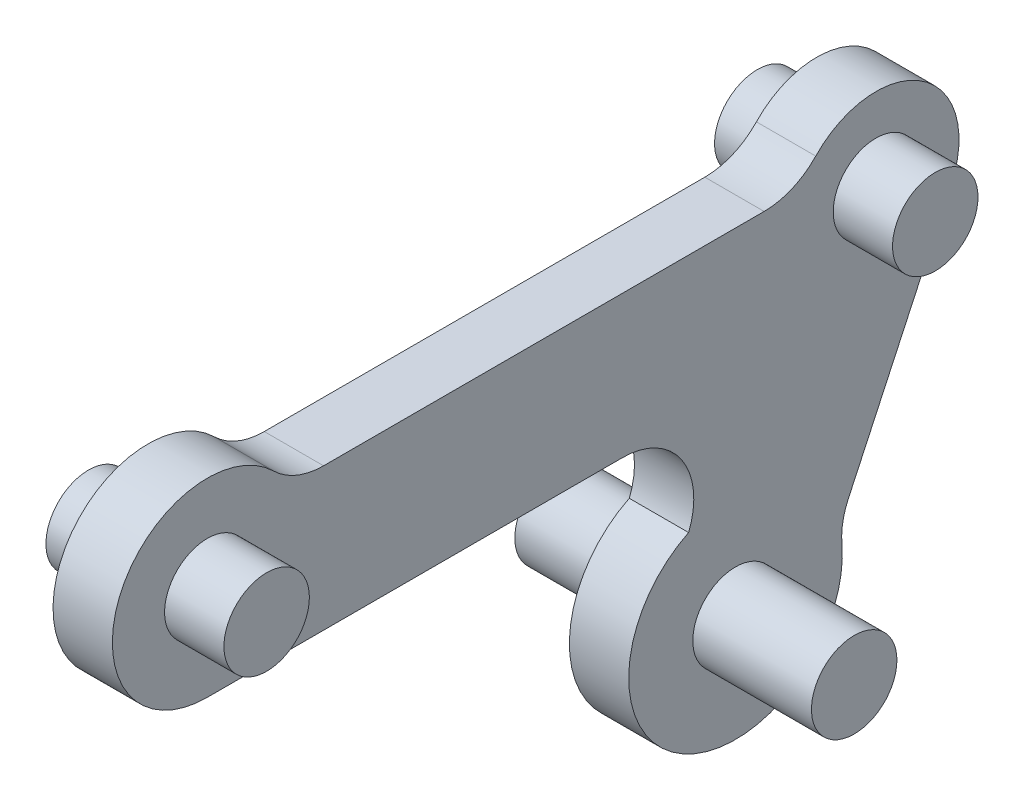
SolidWorks part; units mm, degrees
ref_plane "前视基准面" through (0, 0, 0) normal (0, 0, 1) x (1, 0, 0)
ref_plane "上视基准面" through (0, 0, 0) normal (0, 1, 0) x (1, 0, 0)
ref_plane "右视基准面" through (0, 0, 0) normal (1, 0, 0) x (0, 0, -1)
other "Configuration Table"
sketch "草图1" plane through (0, 0, 0) normal (1, 0, 0) x (0, 0, -1)
  line L1 (-28.1721, 1.4792) -> (-3.1721, 1.4792)
  line L2 (-28.1721, 1.4792) -> (-28.1721, -4.5208)
  line L3 (-28.1721, -4.5208) -> (-3.1721, -4.5208)
  line L4 (-3.1721, 1.4792) -> (-3.1721, -4.5208)
  line L5 (-3.1721, 1.4792) -> (3.1721, -1.4792)
  line L6 (-3.1721, 1.4792) -> (-9.0887, -11.2091)
  line L7 (-9.0887, -11.2091) -> (-2.7446, -14.1675)
  line L8 (3.1721, -1.4792) -> (-2.7446, -14.1675)
  circle A0 centre (-28.1721, -0.5208) radius 4
  circle A1 centre (0, 0) radius 3.5
  circle A2 centre (-5.9167, -12.6883) radius 4.5
  circle A3 centre (-28.1721, -0.5208) radius 2
  circle A4 centre (0, 0) radius 2
  circle A5 centre (-5.9167, -12.6883) radius 2
  point P18 (0, 0)
  point P19 (0, 0)
  point P22 (0, 0)
  point P23 (0, 0)
  dimension "D5" = 8
  dimension "D6" = 7
  dimension "D7" = 9
  dimension "D9" = 4
  dimension "D1" = 6
  dimension "D3" = 65
  dimension "D4" = 25
  dimension "D8" = 14
extrude "凸台-拉伸1" add sketch "草图1" along normal blind 1.25 contours A0 | L1 L4 L3 L2 | A1 | L5 L8 L7 L6 | A2
extrude "切除-拉伸1" cut sketch "草图1<3>" along normal through all contours A3 | A4 | A5
sketch "草图1<3>" plane through (0, 0, 0) normal (1, 0, 0) x (0, 0, -1) same geometry as "草图1"
fillet "圆角1" radius 3 5 edges at (0.625, -11.604, 1.5492) (0.625, -1.4792, -3.1721) (0.625, 1.4792, 3.1721) (0.625, 1.4792, 24.708) (0.625, -4.5208, 5.9699)
sketch "草图2" plane through (1.25, 0, 0) normal (1, 0, 0) x (0, 0, -1)
  circle A0 centre (0, 0) radius 2
  circle A1 centre (-5.9167, -12.6883) radius 2
  circle A2 centre (-28.1721, -0.5208) radius 2
  circle A3 centre (0, 0) radius 1.8
  circle A4 centre (-5.9167, -12.6883) radius 1.8
  circle A5 centre (-28.1721, -0.5208) radius 1.8
  dimension "D1" = 4
  dimension "D2" = 3.6
extrude "凸台-拉伸2" add sketch "草图2" against normal up to surface (1.25 mm away) contours A2 | A0 | A1 up to face at (0, -0.5208, 26.1721)
extrude "凸台-拉伸5" add sketch "草图2<5>" along normal blind 2.5 contours A5 | A3 region at (1.25, 0, 0) region at (1.25, -0.5208, 28.1721)
sketch "草图2<5>" plane through (1.25, 0, 0) normal (1, 0, 0) x (0, 0, -1) same geometry as "草图2"
extrude "凸台-拉伸7" add sketch "草图2<7>" along normal blind 5 contours A4 region at (1.25, -12.6883, 5.9167)
sketch "草图2<7>" plane through (1.25, 0, 0) normal (1, 0, 0) x (0, 0, -1) same geometry as "草图2"
ref_plane "基准面1" through (0, 0, 0) normal (-1, 0, 0) x (0, 0, 1)
mirror "镜向1" about plane through (0, 0, 0) normal (-1, 0, 0) of bodies 113
